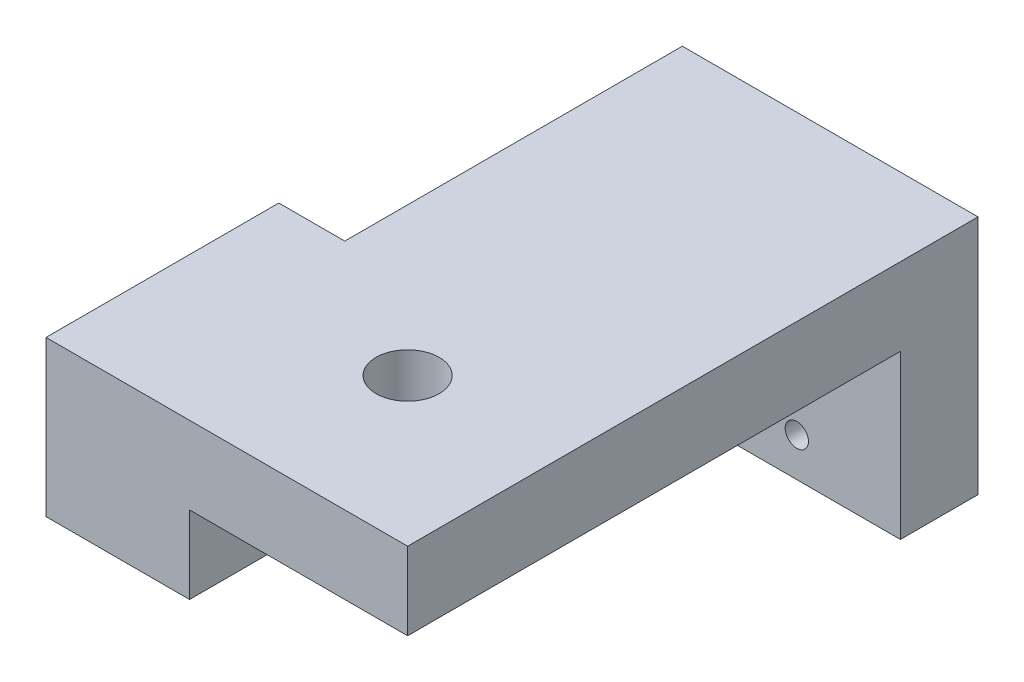
SolidWorks part; units mm, degrees
ref_plane "Front Plane" through (0, 0, 0) normal (0, 0, 1) x (1, 0, 0)
ref_plane "Top Plane" through (0, 0, 0) normal (0, 1, 0) x (1, 0, 0)
ref_plane "Right Plane" through (0, 0, 0) normal (1, 0, 0) x (0, 0, -1)
sketch "Sketch1" plane through (0, 0, 0) normal (0, 1, 0) x (1, 0, 0)
  line L1 (0, 0) -> (38.1, 0)
  line L2 (0, 0) -> (0, -63.5)
  line L3 (0, -63.5) -> (38.1, -63.5)
  line L4 (38.1, 0) -> (38.1, -63.5)
  circle A0 centre (19.05, -44.45) radius 4.064
  dimension "D2" = 8.128
  dimension "D1" = 38.1
  dimension "D3" = 19.05
  dimension "D4" = 19.05
  dimension "D5" = 63.5
extrude "Boss-Extrude1" add sketch "Sketch1" along normal blind 10
sketch "Sketch2" plane through (0, 0, 0) normal (1, 0, 0) x (0, 0, -1)
  line L1 (-63.5, 0) -> (0, 0) construction
  line L2 (-33.5, 0) -> (-33.5, -10)
  line L3 (-33.5, -10) -> (-63.5, -10)
  line L4 (-63.5, -10) -> (-63.5, 0)
  line L5 (-63.5, 10) -> (0, 10) construction
  line L6 (-63.5, 0) -> (-63.5, 10)
  line L7 (-63.5, 10) -> (-33.5, 10)
  line L8 (-33.5, 10) -> (-33.5, 0)
  circle A0 centre (-59.6, 8) radius 1.5
  circle A1 centre (-37.4, -2.3) radius 1.5
  dimension "D3" = 3
  dimension "D2" = 30
  dimension "D4" = 10.3
  dimension "D5" = 22.2
  dimension "D6" = 3.9
  dimension "D1" = 2
  dimension "D7" = 20
extrude "Boss-Extrude2" add sketch "Sketch2" along normal blind 10 and the other way blind 8.5
sketch "Sketch3" plane through (0, 0, 0) normal (0, 0, 1) x (1, 0, 0)
  line L0 (13.25, -3) -> (16.25, -3)
  line L1 (0, 10) -> (38.1, 10)
  line L2 (0, 10) -> (0, -21)
  line L3 (0, -21) -> (38.1, -21)
  line L4 (38.1, 10) -> (38.1, -21)
  line L6 (38.1, 10) -> (38.1, 0) construction
  line L7 (-8.5, 10) -> (38.1, 10) construction
  line L8 (13.25, -21) -> (13.25, -3)
  line L14 (16.25, -3) -> (16.25, -21)
  circle A0 centre (4.75, 4) radius 1.5
  circle A1 centre (24.75, 4) radius 1.5
  circle A2 centre (24.75, -16) radius 1.5
  circle A3 centre (4.75, -16) radius 1.5
  dimension "D6" = 3
  dimension "D1" = 20
  dimension "D2" = 20
  dimension "D3" = 5
  dimension "D4" = 4.75
  dimension "D5" = 6
  dimension "D7" = 3
  dimension "D8" = 18
  dimension "D9" = 8.5
  dimension "D10" = 8.5
extrude "Boss-Extrude3" add sketch "Sketch3" against normal blind 10 contours L14 L3 L4 L1 L2 L8 A3 A2 A1 A0 region at (19.372, -5.1677, 0)
extrude "Cut-Extrude1" cut sketch "Sketch2<2>" along normal blind 10 contours A0 region at (0, 8, 59.6)
sketch "Sketch2<2>" plane through (0, 0, 0) normal (1, 0, 0) x (0, 0, -1) same geometry as "Sketch2"
extrude "Cut-Extrude2" cut sketch "Sketch3<2>" along normal blind 10 contours A1 | A0 region at (4.75, 4, 0) region at (24.75, 4, 0)
sketch "Sketch3<2>" plane through (0, 0, 0) normal (0, 0, 1) x (1, 0, 0) same geometry as "Sketch3"
equation "\"D6@Sketch2\"=(\"D2@Sketch2\"-\"D5@Sketch2\")/2"
